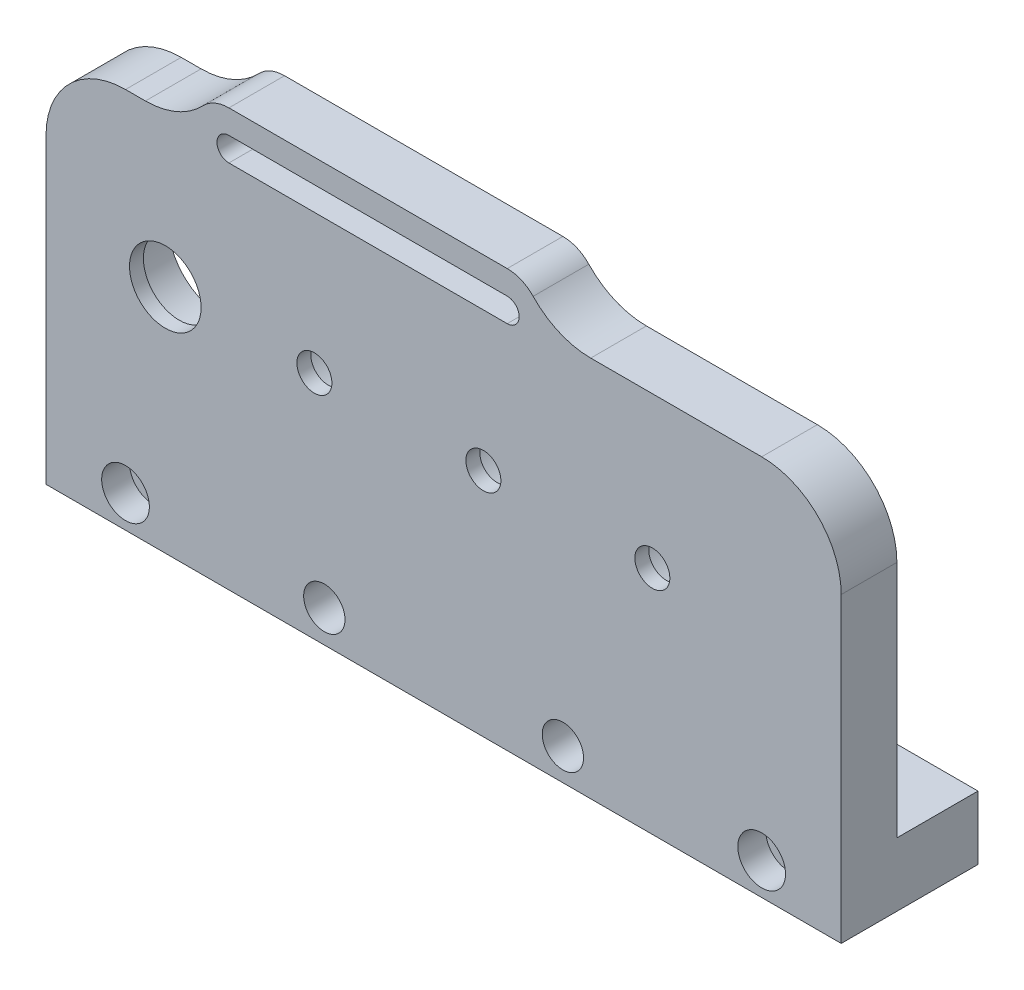
SolidWorks part; units mm, degrees
ref_plane "Front Plane" through (0, 0, 0) normal (0, 0, 1) x (1, 0, 0)
ref_plane "Top Plane" through (0, 0, 0) normal (0, 1, 0) x (1, 0, 0)
ref_plane "Right Plane" through (0, 0, 0) normal (1, 0, 0) x (0, 0, -1)
sketch "Sketch1" plane through (0, 0, 0) normal (0, 0, 1) x (1, 0, 0)
  line L1 (0, 0) -> (100, 0)
  line L2 (0, 0) -> (0, 48)
  line L3 (0, 48) -> (100, 48)
  line L4 (100, 0) -> (100, 48)
  dimension "D1" = 100
  dimension "D2" = 48
extrude "Boss-Extrude1" add sketch "Sketch1" along normal blind 7
sketch "Sketch2" plane through (0, 0, 7) normal (0, 0, 1) x (1, 0, 0)
  line L0 (0, 0) -> (100, 0) construction
  line L1 (0, 48) -> (0, 0) construction
  circle A0 centre (15, 29) radius 4.5
  circle A1 centre (33.75, 29) radius 2.2
  circle A2 centre (55, 29) radius 2.2
  circle A3 centre (76.25, 29) radius 2.2
  dimension "D1" = 4.4
  dimension "D2" = 18.75
  dimension "D3" = 21.25
  dimension "D4" = 21.25
  dimension "D5" = 29
  dimension "D6" = 15
  dimension "D7" = 9
extrude "Cut-Extrude1" cut sketch "Sketch2" against normal up to next
sketch "Sketch3" plane through (0, 0, 0) normal (0, 0, -1) x (-1, 0, 0)
  line L0 (0, 48) -> (0, 0) construction
  line L1 (-100, 0) -> (0, 0)
  line L2 (-100, 0) -> (-100, 8)
  line L3 (-100, 8) -> (0, 8)
  line L4 (0, 0) -> (0, 8)
  dimension "D1" = 8
extrude "Boss-Extrude2" add sketch "Sketch3" along normal blind 10.2
sketch "Sketch4" plane through (0, 0, 0) normal (0, 0, -1) x (-1, 0, 0)
  circle A0 centre (-76.25, 29) radius 6.6
  circle A1 centre (-55, 29) radius 6.6
  circle A2 centre (-33.75, 29) radius 6.6
  circle A3 centre (-15, 29) radius 6.6
  dimension "D1" = 13.2
extrude "Cut-Extrude2" cut sketch "Sketch4" against normal blind 5.25
sketch "Sketch5" plane through (0, 0, 7) normal (0, 0, 1) x (1, 0, 0)
  line L0 (35, 4.0521) -> (65, 4) construction
  line L1 (0, 0) -> (100, 0) construction
  circle A0 centre (35, 4.0521) radius 2.6
  circle A1 centre (65, 4) radius 2.6
  point P6 (50, 0)
  point P7 (50, 4.0261)
  dimension "D1" = 5.2
  dimension "D2" = 30
  dimension "D3" = 4
extrude "Cut-Extrude3" cut sketch "Sketch5" against normal blind 7
sketch "Sketch7" plane through (0, 0, 0) normal (0, 0, 1) x (1, 0, 0)
  circle A0 centre (35, 4.0521) radius 1.5
  circle A1 centre (65, 4) radius 1.5
  dimension "D1" = 3
extrude "Cut-Extrude4" cut sketch "Sketch7" against normal through all
sketch "Sketch8" plane through (0, 0, 7) normal (0, 0, 1) x (1, 0, 0)
  line L0 (10, 4.0521) -> (35, 4.0521) construction
  line L1 (0, 48) -> (0, 0) construction
  line L2 (100, 0) -> (100, 48) construction
  circle A0 centre (10, 4.0521) radius 1.7
  circle A1 centre (90, 4.0521) radius 1.7
  dimension "D1" = 3.4
  dimension "D2" = 10
  dimension "D3" = 10
extrude "Cut-Extrude5" cut sketch "Sketch8" against normal up to next
sketch "Sketch9" plane through (0, 0, 7) normal (0, 0, 1) x (1, 0, 0)
  circle A0 centre (10, 4.0521) radius 3
  circle A1 centre (90, 4.0521) radius 3
  dimension "D1" = 6
extrude "Cut-Extrude6" cut sketch "Sketch9" against normal blind 3.5
sketch "Sketch10" plane through (0, 0, 7) normal (0, 0, 1) x (1, 0, 0)
  line L0 (23, 48) -> (58, 48) construction
  line L1 (100, 48) -> (0, 48) construction
  line L2 (23, 49.5) -> (58, 49.5)
  line L3 (23, 46.5) -> (58, 46.5)
  line L4 (23, 52.5) -> (58, 52.5)
  line L5 (23, 43.5) -> (58, 43.5)
  line L6 (0, 48) -> (0, 0) construction
  arc A0 (23, 49.5) -> (23, 46.5) centre (23, 48) ccw
  arc A1 (58, 46.5) -> (58, 49.5) centre (58, 48) ccw
  arc A2 (58, 43.5) -> (58, 52.5) centre (58, 48) ccw
  arc A3 (23, 52.5) -> (23, 43.5) centre (23, 48) ccw
  point P4 (40.5, 48)
  dimension "D3" = 35
  dimension "D2" = 3
  dimension "D4" = 23
  dimension "D1" = 3
extrude "Boss-Extrude3" add sketch "Sketch10" against normal up to surface (7 mm away) up to face at (69.65, 29, 0)
sketch "Sketch11" plane through (0, 0, 7) normal (0, 0, 1) x (1, 0, 0)
  line L0 (23, 48) -> (58, 48) construction
  line L1 (59.5, 48) -> (21.5, 48) construction
  line L2 (23, 49.5) -> (58, 49.5)
  line L3 (23, 46.5) -> (58, 46.5)
  arc A0 (23, 49.5) -> (23, 46.5) centre (23, 48) ccw
  arc A1 (58, 46.5) -> (58, 49.5) centre (58, 48) ccw
  point P5 (40.5, 48)
  dimension "D1" = 3
extrude "Cut-Extrude7" cut sketch "Sketch11" against normal up to next
fillet "Fillet1" radius 10 2 edges at (0, 48, 3.5) (100, 48, 3.5)
fillet "Fillet2" radius 10 2 edges at (62.5, 48, 3.5) (18.5, 48, 3.5)
